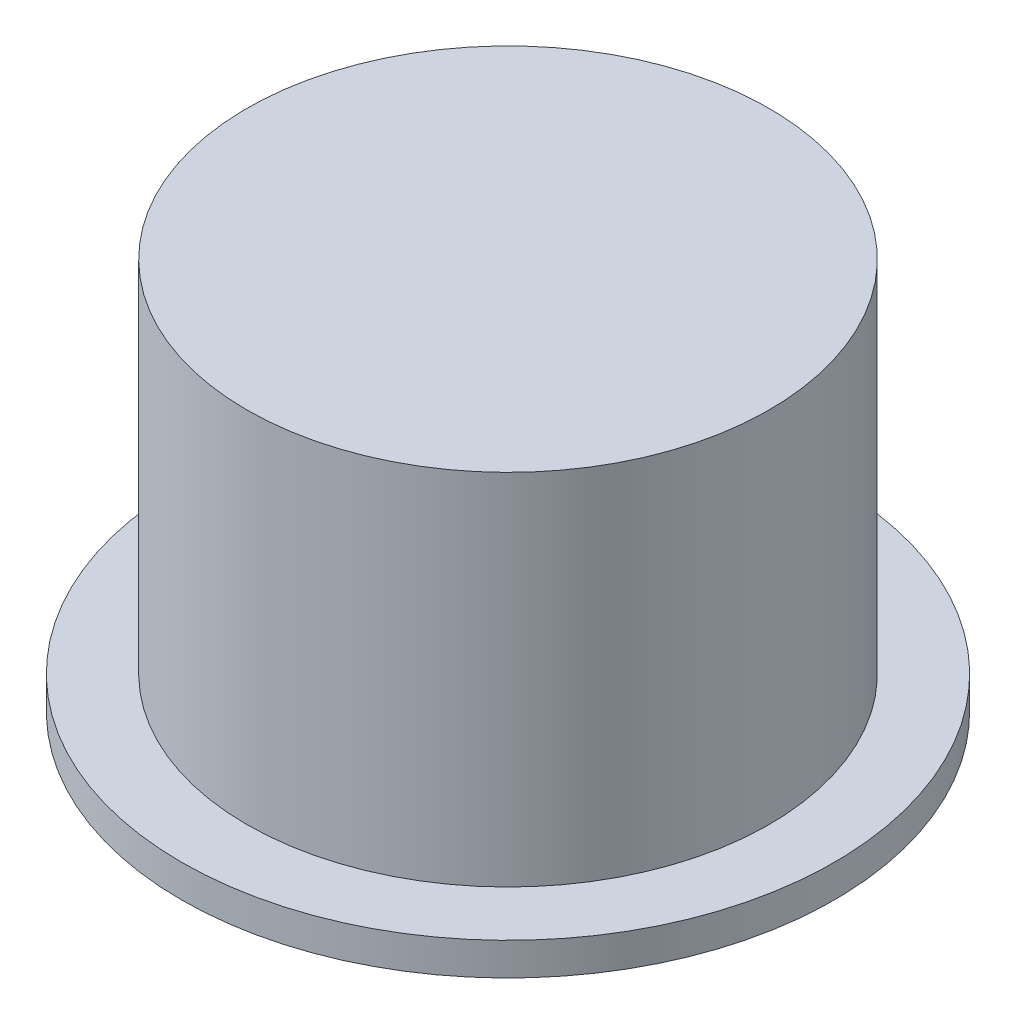
SolidWorks part; units mm, degrees
ref_plane "Front" through (0, 0, 0) normal (0, 0, 1) x (1, 0, 0)
ref_plane "Top" through (0, 0, 0) normal (0, 1, 0) x (1, 0, 0)
ref_plane "Right" through (0, 0, 0) normal (1, 0, 0) x (0, 0, -1)
other "Configuration Table"
sketch "Sketch1" plane through (0, 0, 0) normal (0, 1, 0) x (1, 0, 0)
  circle A0 centre (0, 0) radius 5
  circle A1 centre (0, 0) radius 4
  dimension "D1" = 10
  dimension "D2" = 8
extrude "Boss-Extrude1" add sketch "Sketch1" along normal blind 0.5
extrude "Boss-Extrude2" add sketch "Sketch1<3>" along normal blind 6 contours A1 region at (0, 0, 0)
sketch "Sketch1<3>" plane through (0, 0, 0) normal (0, 1, 0) x (1, 0, 0) same geometry as "Sketch1"
